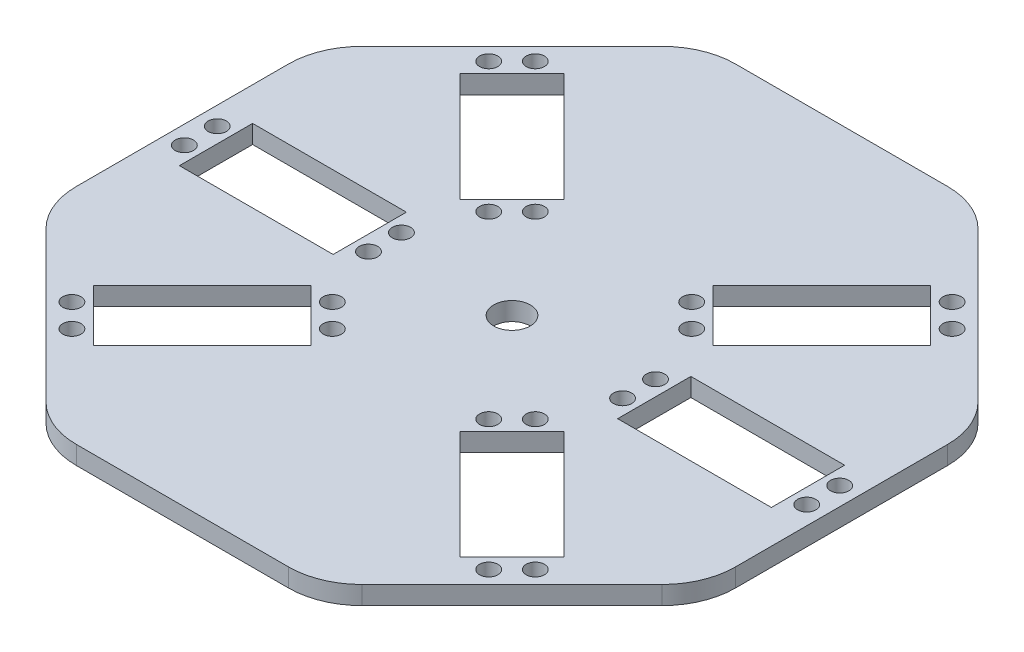
SolidWorks part; units mm, degrees
ref_plane "Front Plane" through (0, 0, 0) normal (0, 0, 1) x (1, 0, 0)
ref_plane "Top Plane" through (0, 0, 0) normal (0, 1, 0) x (1, 0, 0)
ref_plane "Right Plane" through (0, 0, 0) normal (1, 0, 0) x (0, 0, -1)
sketch "Sketch1" plane through (0, 0, 0) normal (0, 1, 0) x (1, 0, 0)
  line L0 (21.3546, -27.7186) -> (56.9221, -63.2861)
  line L1 (-90, -37.2792) -> (-37.2792, -90)
  line L2 (-37.2792, -90) -> (37.2792, -90)
  line L3 (37.2792, -90) -> (90, -37.2792)
  line L4 (90, -37.2792) -> (90, 37.2792)
  line L5 (90, 37.2792) -> (37.2792, 90)
  line L6 (37.2792, 90) -> (-37.2792, 90)
  line L7 (-37.2792, 90) -> (-90, 37.2792)
  line L8 (-90, 37.2792) -> (-90, -37.2792)
  line L9 (21.3546, -27.7186) -> (27.7186, -21.3546)
  line L10 (56.9221, -63.2861) -> (63.2861, -56.9221)
  line L11 (27.7186, -21.3546) -> (63.2861, -56.9221)
  line L12 (63.6396, -63.6396) -> (0, 0) construction
  line L13 (34.5422, -20.4) -> (20.4, -34.5422)
  line L14 (34.5422, -20.4) -> (64.2407, -50.0985)
  line L15 (20.4, -34.5422) -> (50.0985, -64.2407)
  line L16 (64.2407, -50.0985) -> (50.0985, -64.2407)
  line L17 (10, -38.85) -> (-10, -38.85) [skipped]
  line L18 (10, -38.85) -> (10, -80.85) [skipped]
  line L19 (10, -80.85) -> (-10, -80.85) [skipped]
  line L20 (-10, -38.85) -> (-10, -80.85) [skipped]
  line L21 (-20.4, -34.5422) -> (-34.5422, -20.4)
  line L22 (-20.4, -34.5422) -> (-50.0985, -64.2407)
  line L23 (-50.0985, -64.2407) -> (-64.2407, -50.0985)
  line L24 (-34.5422, -20.4) -> (-64.2407, -50.0985)
  line L25 (-38.85, -10) -> (-38.85, 10)
  line L26 (-38.85, -10) -> (-80.85, -10)
  line L27 (-80.85, -10) -> (-80.85, 10)
  line L28 (-38.85, 10) -> (-80.85, 10)
  line L29 (-34.5422, 20.4) -> (-20.4, 34.5422)
  line L30 (-34.5422, 20.4) -> (-64.2407, 50.0985)
  line L31 (-64.2407, 50.0985) -> (-50.0985, 64.2407)
  line L32 (-20.4, 34.5422) -> (-50.0985, 64.2407)
  line L33 (-10, 38.85) -> (10, 38.85) [skipped]
  line L34 (-10, 38.85) -> (-10, 80.85) [skipped]
  line L35 (-10, 80.85) -> (10, 80.85) [skipped]
  line L36 (10, 38.85) -> (10, 80.85) [skipped]
  line L37 (20.4, 34.5422) -> (34.5422, 20.4)
  line L38 (20.4, 34.5422) -> (50.0985, 64.2407)
  line L39 (50.0985, 64.2407) -> (64.2407, 50.0985)
  line L40 (34.5422, 20.4) -> (64.2407, 50.0985)
  line L41 (38.85, 10) -> (38.85, -10)
  line L42 (38.85, 10) -> (80.85, 10)
  line L43 (80.85, 10) -> (80.85, -10)
  line L44 (38.85, -10) -> (80.85, -10)
  circle A0 centre (0, 0) radius 90 construction
  circle A5 centre (56.9221, -63.2861) radius 2.5
  circle A6 centre (63.2861, -56.9221) radius 2.5
  circle A7 centre (27.7186, -21.3546) radius 2.5
  circle A8 centre (21.3546, -27.7186) radius 2.5
  circle A9 centre (-4.5, -34.7) radius 2.5 [skipped]
  circle A10 centre (4.5, -34.7) radius 2.5 [skipped]
  circle A11 centre (4.5, -85) radius 2.5 [skipped]
  circle A12 centre (-4.5, -85) radius 2.5 [skipped]
  circle A13 centre (0, 0) radius 90 construction
  circle A14 centre (-27.7186, -21.3546) radius 2.5
  circle A15 centre (-21.3546, -27.7186) radius 2.5
  circle A16 centre (-56.9221, -63.2861) radius 2.5
  circle A17 centre (-63.2861, -56.9221) radius 2.5
  circle A18 centre (0, 0) radius 90 construction
  circle A19 centre (-34.7, 4.5) radius 2.5
  circle A20 centre (-34.7, -4.5) radius 2.5
  circle A21 centre (-85, -4.5) radius 2.5
  circle A22 centre (-85, 4.5) radius 2.5
  circle A23 centre (0, 0) radius 90 construction
  circle A24 centre (-21.3546, 27.7186) radius 2.5
  circle A25 centre (-27.7186, 21.3546) radius 2.5
  circle A26 centre (-63.2861, 56.9221) radius 2.5
  circle A27 centre (-56.9221, 63.2861) radius 2.5
  circle A28 centre (0, 0) radius 90 construction
  circle A29 centre (4.5, 34.7) radius 2.5 [skipped]
  circle A30 centre (-4.5, 34.7) radius 2.5 [skipped]
  circle A31 centre (-4.5, 85) radius 2.5 [skipped]
  circle A32 centre (4.5, 85) radius 2.5 [skipped]
  circle A33 centre (0, 0) radius 90 construction
  circle A34 centre (27.7186, 21.3546) radius 2.5
  circle A35 centre (21.3546, 27.7186) radius 2.5
  circle A36 centre (56.9221, 63.2861) radius 2.5
  circle A37 centre (63.2861, 56.9221) radius 2.5
  circle A38 centre (0, 0) radius 90 construction
  circle A39 centre (34.7, -4.5) radius 2.5
  circle A40 centre (34.7, 4.5) radius 2.5
  circle A41 centre (85, 4.5) radius 2.5
  circle A42 centre (85, -4.5) radius 2.5
  circle A43 centre (0, 0) radius 90 construction
  point P15 (63.6396, -63.6396)
  point P16 (60.1041, -60.1041)
  point P17 (57.1696, -57.1696)
  point P121 (0, 0)
  dimension "D4" = 5
  dimension "D5" = 5
  dimension "D6" = 5
  dimension "D7" = 5
  dimension "D1" = 90
  dimension "D2" = 9
  dimension "D3" = 50.3
  dimension "D8" = 5
  dimension "D9" = 42
  dimension "D10" = 20
  dimension "D11" = 4.15
  dimension "D12" = 8
extrude "Boss-Extrude1" add sketch "Sketch1" along normal blind 5 contours L11 A7 L9 | L9 A7 L11 | L9 A8 L0 | L0 A8 L9 | L11 A6 L10 | L10 A6 L11 | L10 A5 L0 | L0 A5 L10 | L16 L14 L13 L11 | L16 L11 L13 L0 | L16 L0 L13 L15 | L37 L40 L39 L38 | L41 L44 L43 L42 | L29 L32 L31 L30 | L25 L28 L27 L26 | L21 L24 L23 L22 | A22 | A21 | A19 | A20 | A26 | A27 | A24 | A25 | A35 | A34 | A40 | A39 | A41 | A42 | A17 | A16 | A14 | A36 | A37 | L8 L1 L2 L3 L4 L5 L6 L7 | A15 region at (22.8552, 0, 27.7186) region at (20.8544, 0, 27.7186) region at (42.3203, 0, 42.3203) region at (37.1938, 0, 47.4469) region at (27.7186, 0, 20.8544) region at (27.7186, 0, 22.8552) region at (47.4469, 0, 37.1938) region at (56.9221, 0, 61.7855) region at (56.9221, 0, 63.7862) region at (63.7862, 0, 56.9221) region at (61.7855, 0, 56.9221) region at (-42.3203, 0, 42.3203) region at (-59.85, 0, 0) region at (-42.3203, 0, -42.3203) region at (42.3203, 0, -42.3203) region at (59.85, 0, 0) region at (-27.7186, 0, 21.3546) region at (-56.9221, 0, 63.2861) region at (-63.2861, 0, 56.9221) region at (-34.7, 0, -4.5) region at (-34.7, 0, 4.5) region at (-85, 0, 4.5) region at (-85, 0, -4.5) region at (-21.3546, 0, -27.7186) region at (-27.7186, 0, -21.3546) region at (-63.2861, 0, -56.9221) region at (-56.9221, 0, -63.2861) region at (27.7186, 0, -21.3546) region at (21.3546, 0, -27.7186) region at (56.9221, 0, -63.2861) region at (63.2861, 0, -56.9221) region at (34.7, 0, 4.5) region at (34.7, 0, -4.5) region at (85, 0, -4.5) region at (85, 0, 4.5)
fillet "Fillet1" radius 20 8 edges at (-90, 2.5, -37.2792) (-37.2792, 2.5, -90) (37.2792, 2.5, -90) (90, 2.5, -37.2792) (90, 2.5, 37.2792) (37.2792, 2.5, 90) (-37.2792, 2.5, 90) (-90, 2.5, 37.2792)
sketch "Sketch2" plane through (0, 5, 0) normal (0, 1, 0) x (1, 0, 0)
  circle A0 centre (0, 0) radius 5
  dimension "D1" = 10
extrude "Cut-Extrude1" cut sketch "Sketch2" against normal through all
